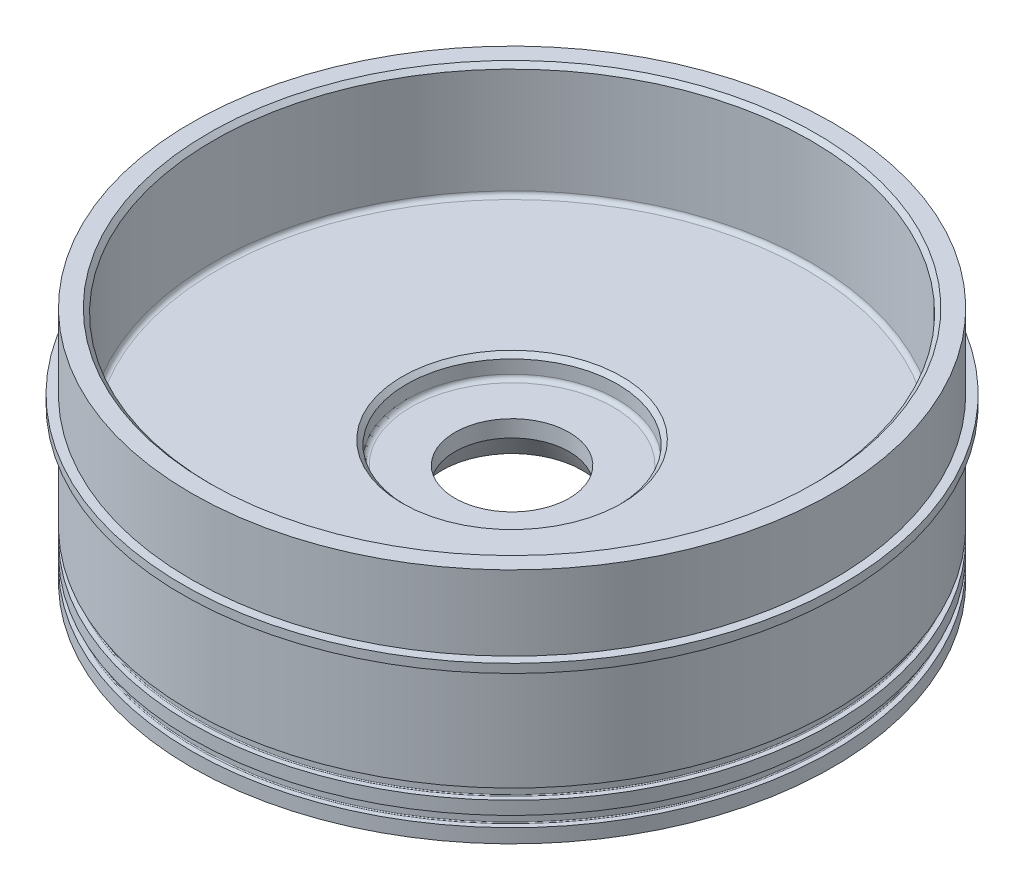
SolidWorks part; units mm, degrees
material "6061-T6 (SS)"
ref_plane "Piano frontale" through (0, 0, 0) normal (0, 0, 1) x (1, 0, 0)
ref_plane "Piano superiore" through (0, 0, 0) normal (0, 1, 0) x (1, 0, 0)
ref_plane "Piano destro" through (0, 0, 0) normal (1, 0, 0) x (0, 0, -1)
sketch "Schizzo1" plane through (0, 0, 0) normal (0, 0, 1) x (1, 0, 0)
  line L0 (0, 0) -> (0, 25.5769) construction
  line L1 (-13, 0) -> (-73, 0)
  line L2 (-73, 0) -> (-73, 14)
  line L3 (-73, 14) -> (-24, 14)
  line L4 (-24, 14) -> (-24, 9)
  line L5 (-24, 9) -> (-13, 9)
  line L6 (-13, 9) -> (-13, 0)
  line L7 (-24, 14) -> (-13, 14)
  line L8 (-13, 14) -> (-13, 9)
  line L9 (-73, 14) -> (-73, 40)
  line L10 (-73, 40) -> (-68, 40)
  line L11 (-69, 0) -> (-69, -14)
  line L12 (-69, -14) -> (-73, -14)
  line L13 (-73, -14) -> (-73, 0)
  line L14 (-68, 14) -> (-68, 40)
  line L15 (-73, 23) -> (-75, 23)
  line L16 (-75, 23) -> (-75, 21)
  line L17 (-73, -14) -> (-73, 0)
  line L18 (-73, -3) -> (-71.7, -3)
  line L19 (-71.7, -3) -> (-71.7, -5.4)
  line L20 (-71.7, -5.4) -> (-73, -5.4)
  line L21 (-73, -8.4) -> (-71.7, -8.4)
  line L22 (-71.7, -8.4) -> (-71.7, -10.8)
  line L23 (-71.7, -10.8) -> (-73, -10.8)
  line L24 (-75, 21) -> (-73, 21)
  dimension "D1" = 5
  dimension "D2" = 146
  dimension "D3" = 26
  dimension "D4" = 48
  dimension "D5" = 14
  dimension "D6" = 4
  dimension "D7" = 2.4
  dimension "D8" = 1.3
  dimension "D9" = 3
  dimension "D10" = 3
  dimension "D11" = 14
  dimension "D12" = 26
  dimension "D13" = 136
  dimension "D14" = 2
  dimension "D15" = 150
  dimension "D16" = 35
revolve "Rivoluzione1" add sketch "Schizzo1" angle 360 about L0 region at (-44.7166, 6.6847, 0) region at (-70.8307, -7.0125, 0) region at (-18.5, 11.5, 0) region at (-70.5, 27, 0) region at (-74, 22, 0)
chamfer "Smusso1" distance 3 angle 60 1 edges at (0, 0, -13) first distance on face at (0, 0, -69)
chamfer "Smusso2" distance 1 angle 45 1 edges at (0, -14, -69)
fillet "Raccordo1" radius 1 2 edges at (0, 0, -69) (0, 14, -68)
chamfer "Smusso3" distance 1 angle 45 1 edges at (0, 40, -68)
fillet "Raccordo2" radius 0.2 4 edges at (0, -8.4, -71.7) (0, -10.8, -71.7) (0, -3, -71.7) (0, -5.4, -71.7)
sketch "Schizzo2" plane through (0, 0, 0) normal (0, 0, 1) x (1, 0, 0)
  line L0 (0, 0) -> (0, 58.1242) construction
  line L1 (0, 0) -> (-27.2443, 0) construction
  line L2 (-68, 0) -> (68, 0) construction
  line L3 (-13, 9) -> (-24, 9)
  line L4 (-24, 9) -> (-24, 14)
  line L5 (67, 14) -> (-67, 14) construction
  line L6 (-24, 14) -> (-13, 14)
  line L7 (13, 14) -> (-13, 14) construction
  line L8 (-13, 14) -> (-13, 9)
  line L9 (-13, 9) -> (-13, 0) construction
  point P14 (-13, 8.4408)
  dimension "D1" = 5
  dimension "D2" = 48
revolve "Taglia-Rivoluzione1" cut sketch "Schizzo2" angle 360 about L0
fillet "Raccordo3" radius 1 1 edges at (0, 9, -24)
chamfer "Smusso4" distance 1 angle 45 1 edges at (0, 14, -24)
